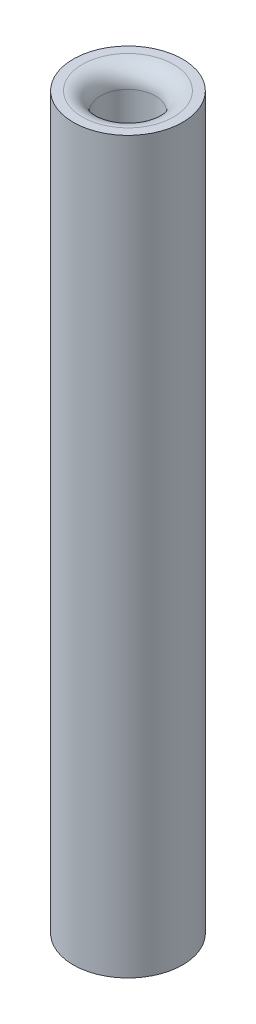
SolidWorks part; units mm, degrees
ref_plane "Front Plane" through (0, 0, 0) normal (0, 0, 1) x (1, 0, 0)
ref_plane "Top Plane" through (0, 0, 0) normal (0, 1, 0) x (1, 0, 0)
ref_plane "Right Plane" through (0, 0, 0) normal (1, 0, 0) x (0, 0, -1)
sketch "Sketch2" plane through (0, 0, 0) normal (0, 1, 0) x (1, 0, 0)
  circle A0 centre (-15.0841, 6.4658) radius 1.5
  circle A1 centre (-15.0841, 6.4658) radius 3
  dimension "D1" = 3
  dimension "D2" = 6
extrude "Boss-Extrude1" add sketch "Sketch2" along normal blind 40
fillet "Fillet1" radius 1 2 edges at (-15.0841, 0, -4.9658) (-15.0841, 40, -4.9658)
